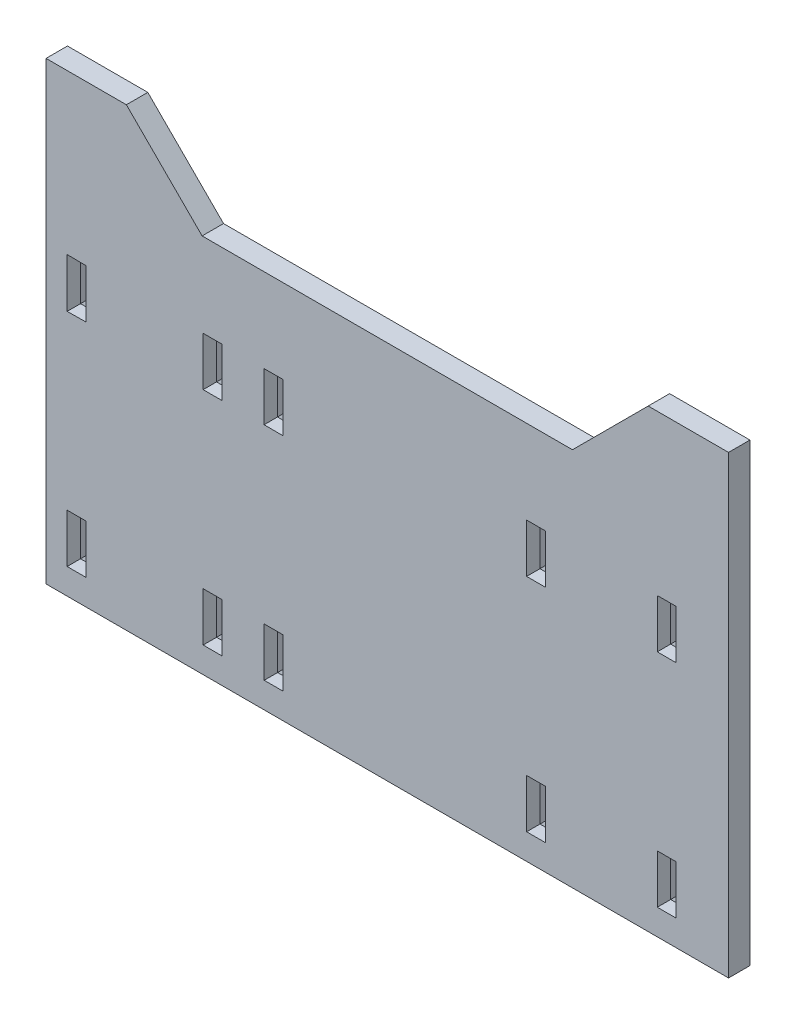
SolidWorks part; units mm, degrees
ref_plane "Front Plane" through (0, 0, 0) normal (0, 0, 1) x (1, 0, 0)
ref_plane "Top Plane" through (0, 0, 0) normal (0, 1, 0) x (1, 0, 0)
ref_plane "Right Plane" through (0, 0, 0) normal (1, 0, 0) x (0, 0, -1)
sketch "Sketch1" plane through (0, 0, 0) normal (0, 0, 1) x (1, 0, 0)
  line L6 (-34.3851, 25.207) -> (-30.8551, 25.207)
  line L7 (26.0149, 25.207) -> (29.5449, 25.207)
  line L8 (26.0149, 25.207) -> (26.0149, 16.093)
  line L9 (26.0149, 16.093) -> (29.5449, 16.093)
  line L10 (29.5449, 25.207) -> (29.5449, 16.093)
  line L12 (26.0149, -16.093) -> (29.5449, -16.093)
  line L13 (26.0149, -25.207) -> (26.0149, -16.093)
  line L14 (29.5449, -25.207) -> (29.5449, -16.093)
  line L15 (26.0149, -25.207) -> (29.5449, -25.207)
  line L16 (-19.4551, 25.207) -> (-22.9851, 25.1844)
  line L17 (-19.4551, 25.207) -> (-19.4406, 16.093)
  line L18 (-22.9851, 25.1844) -> (-22.9996, 16.1156)
  line L19 (-19.4406, 16.093) -> (-22.9996, 16.1156)
  line L20 (-19.4551, -16.093) -> (-22.9851, -16.093)
  line L21 (-19.4551, -25.207) -> (-19.4551, -16.093)
  line L22 (-22.9851, -25.207) -> (-22.9851, -16.093)
  line L23 (-19.4551, -25.207) -> (-22.9851, -25.207)
  line L39 (50.4149, 25.207) -> (53.9449, 25.207)
  line L40 (50.4149, 25.207) -> (50.4149, 16.093)
  line L41 (50.4149, 16.093) -> (53.9449, 16.093)
  line L42 (53.9449, 25.207) -> (53.9449, 16.093)
  line L43 (50.4149, -16.093) -> (53.9449, -16.093)
  line L44 (50.4149, -16.093) -> (50.4149, -25.207)
  line L45 (50.4149, -25.207) -> (53.9449, -25.207)
  line L46 (53.9449, -16.093) -> (53.9449, -25.207)
  line L47 (-34.3851, 25.207) -> (-34.3851, 16.093)
  line L48 (-34.3851, 16.093) -> (-30.8551, 16.093)
  line L49 (-30.8551, 25.207) -> (-30.8551, 16.093)
  line L50 (-34.3851, -16.093) -> (-30.8551, -16.093)
  line L51 (-34.3851, -16.093) -> (-34.3851, -25.207)
  line L52 (-34.3851, -25.207) -> (-30.8551, -25.207)
  line L53 (-30.8551, -16.093) -> (-30.8551, -25.207)
  line L60 (-59.785, 25.25) -> (-56.2552, 25.207)
  line L61 (-59.785, 25.25) -> (-59.785, 16.05)
  line L62 (-59.785, 16.05) -> (-56.2552, 16.093)
  line L63 (-56.2552, 25.207) -> (-56.2552, 16.093)
  line L64 (-59.7851, -16.093) -> (-56.2551, -16.093)
  line L65 (-59.7851, -16.093) -> (-59.7851, -25.207)
  line L66 (-59.7851, -25.207) -> (-56.2551, -25.207)
  line L67 (-56.2551, -16.093) -> (-56.2551, -25.207)
  line L80 (-63.7201, 30) -> (63.7201, 30)
  line L81 (63.7201, 30) -> (63.7201, -30)
  line L82 (52.1799, 25.207) -> (52.1799, 16.093) construction
  line L83 (27.7799, 16.093) -> (27.7799, 25.207) construction
  line L84 (-63.7201, 30) -> (-63.7201, -30)
  line L85 (-63.7201, -30) -> (63.7201, -30)
  line L87 (53.2799, 20.65) -> (50.4149, 20.65) construction
  line L88 (29.5449, 20.65) -> (26.0149, 20.65) construction
  line L89 (53.9449, -20.65) -> (50.4149, -20.65) construction
  line L90 (52.1799, -16.093) -> (52.1799, -25.207) construction
  line L91 (27.7799, -16.093) -> (27.7799, -25.207) construction
  line L92 (29.5449, -20.65) -> (26.0149, -20.65) construction
  line L93 (-19.4551, -20.65) -> (-22.9851, -20.65) construction
  line L94 (-21.2201, -16.093) -> (-21.2201, -25.207) construction
  line L95 (-32.6201, -16.093) -> (-32.6201, -25.207) construction
  line L96 (-30.8551, -20.65) -> (-34.3851, -20.65) construction
  line L97 (-56.2551, -20.65) -> (-59.7851, -20.65) construction
  line L98 (-58.0201, -16.093) -> (-58.0201, -25.207) construction
  line L99 (-58.0201, 25.2285) -> (-58.0201, 16.0715) construction
  line L100 (-32.6201, 25.207) -> (-32.6201, 16.093) construction
  line L101 (-21.2201, 25.1957) -> (-21.2201, 16.1043) construction
  line L102 (-56.2552, 20.65) -> (-59.785, 20.65) construction
  line L103 (-34.3851, 20.65) -> (-30.8551, 20.65) construction
  line L104 (-19.4479, 20.65) -> (-22.9923, 20.65) construction
  point P0 (0, 0)
  point P86 (0, 30)
  point P87 (63.7201, 0)
  dimension "D1" = 9.2
  dimension "D2" = 3.53
  dimension "D3" = 127.4402
  dimension "D4" = 60
  dimension "D7" = 11.4
  dimension "D8" = 24.4
  dimension "D5" = 27.7799
  dimension "D6" = 21.2201
  dimension "D10" = 20.65
  dimension "D11" = 20.65
  dimension "D9" = 25.4
extrude "Boss-Extrude1" add sketch "Sketch1" against normal blind 4
sketch "Sketch2" plane through (0, 0, 0) normal (0, 0, 1) x (1, 0, 0)
  line L0 (-63.7201, 30) -> (-63.7201, 55)
  line L1 (-63.7201, 55) -> (-48.7201, 55)
  line L2 (-48.7201, 55) -> (-34.578, 40.8579)
  line L7 (63.7201, 30) -> (-63.7201, 30)
  line L8 (48.7201, 55) -> (63.7201, 55)
  line L9 (63.7201, 55) -> (63.7201, 30)
  line L10 (48.7201, 55) -> (34.578, 40.8579)
  line L11 (34.578, 40.8579) -> (-34.578, 40.8579)
  line L12 (-63.7201, 30) -> (-63.7201, -30) construction
  line L14 (63.7201, -30) -> (63.7201, 30) construction
  dimension "D1" = 25
  dimension "D2" = 15
  dimension "D3" = 135
  dimension "D4" = 20
extrude "Boss-Extrude2" add sketch "Sketch2" against normal blind 4
chamfer "Chamfer1" distance 1.5 distance2 0.5 40 edges at (27.7799, 16.093, -4) (29.5449, 20.65, -4) (26.0149, 20.65, -4) (27.7799, 25.207, -4) (53.9449, 20.65, -4) (52.1799, 16.093, -4) (50.4149, 20.65, -4) (52.1799, 25.207, -4) (52.1799, -25.207, -4) (53.9449, -20.65, -4) (52.1799, -16.093, -4) (50.4149, -20.65, -4) (29.5449, -20.65, -4) (27.7799, -25.207, -4) (26.0149, -20.65, -4) (27.7799, -16.093, -4) (-21.2201, -25.207, -4) (-19.4551, -20.65, -4) (-21.2201, -16.093, -4) (-22.9851, -20.65, -4) (-30.8551, -20.65, -4) (-32.6201, -25.207, -4) (-34.3851, -20.65, -4) (-32.6201, -16.093, -4) (-56.2551, -20.65, -4) (-58.0201, -16.093, -4) (-59.7851, -20.65, -4) (-58.0201, -25.207, -4) (-21.2201, 25.1957, -4) (-19.4479, 20.65, -4) (-21.2201, 16.1043, -4) (-22.9923, 20.65, -4) (-32.6201, 16.093, -4) (-30.8551, 20.65, -4) (-32.6201, 25.207, -4) (-34.3851, 20.65, -4) (-58.0201, 16.0715, -4) (-56.2552, 20.65, -4) (-58.0201, 25.2285, -4) (-59.785, 20.65, -4) first distance on face at (27.7799, 16.093, -2) first distance on face at (29.5449, 20.65, -2) first distance on face at (26.0149, 20.65, -2) first distance on face at (27.7799, 25.207, -2) first distance on face at (53.9449, 20.65, -2) first distance on face at (52.1799, 16.093, -2) first distance on face at (50.4149, 20.65, -2) first distance on face at (52.1799, 25.207, -2) first distance on face at (52.1799, -25.207, -2) first distance on face at (53.9449, -20.65, -2) first distance on face at (52.1799, -16.093, -2) first distance on face at (50.4149, -20.65, -2) first distance on face at (29.5449, -20.65, -2) first distance on face at (27.7799, -25.207, -2) first distance on face at (26.0149, -20.65, -2) first distance on face at (27.7799, -16.093, -2) first distance on face at (-21.2201, -25.207, -2) first distance on face at (-19.4551, -20.65, -2) first distance on face at (-21.2201, -16.093, -2) first distance on face at (-22.9851, -20.65, -2) first distance on face at (-30.8551, -20.65, -2) first distance on face at (-32.6201, -25.207, -2) first distance on face at (-34.3851, -20.65, -2) first distance on face at (-32.6201, -16.093, -2) first distance on face at (-56.2551, -20.65, -2) first distance on face at (-58.0201, -16.093, -2) first distance on face at (-59.7851, -20.65, -2) first distance on face at (-58.0201, -25.207, -2) first distance on face at (-21.2201, 25.1957, -2) first distance on face at (-19.4479, 20.65, -2) first distance on face at (-21.2201, 16.1043, -2) first distance on face at (-22.9923, 20.65, -2) first distance on face at (-32.6201, 16.093, -2) first distance on face at (-30.8551, 20.65, -2) first distance on face at (-32.6201, 25.207, -2) first distance on face at (-34.3851, 20.65, -2) first distance on face at (-58.0201, 16.0715, -2) first distance on face at (-56.2552, 20.65, -2) first distance on face at (-58.0201, 25.2285, -2) first distance on face at (-59.785, 20.65, -2)
equation "\"pin_hole_height\"=9.2"
equation "\"D1@Sketch1\"=\"pin_hole_height\""
equation "\"pin_hole_width\"=3.53"
equation "\"D2@Sketch1\"=\"pin_hole_width\""
